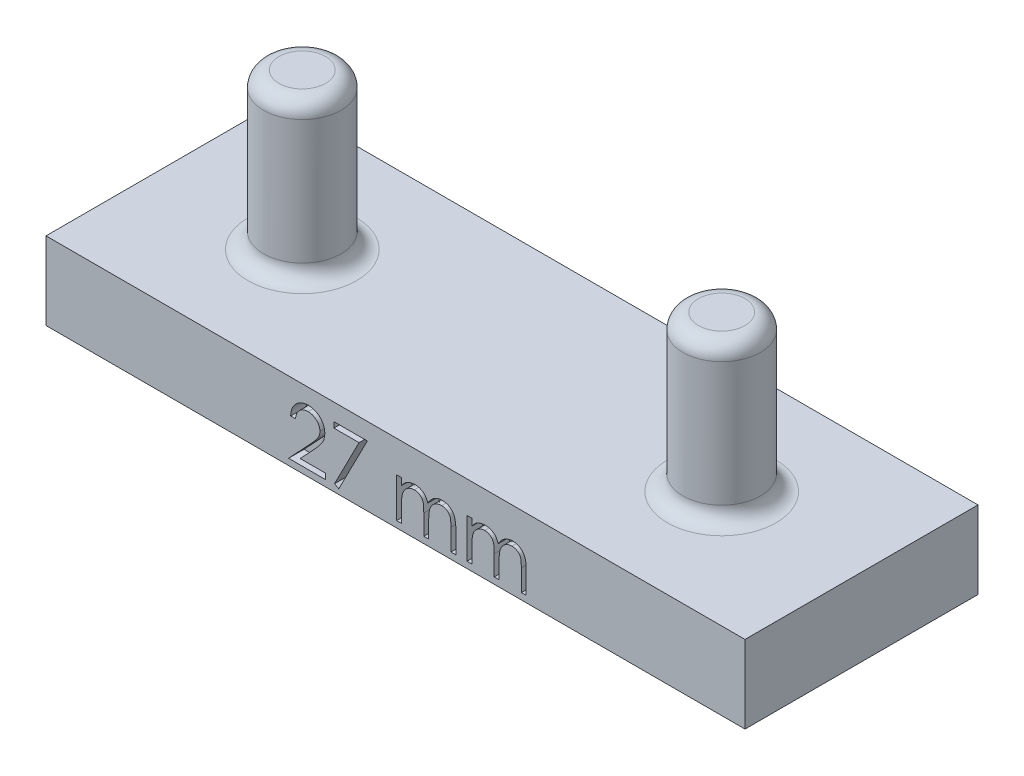
SolidWorks part; units mm, degrees
ref_plane "Front Plane" through (0, 0, 0) normal (0, 0, 1) x (1, 0, 0)
ref_plane "Top Plane" through (0, 0, 0) normal (0, 1, 0) x (1, 0, 0)
ref_plane "Right Plane" through (0, 0, 0) normal (1, 0, 0) x (0, 0, -1)
sketch "Sketch1" plane through (0, 0, 0) normal (0, 1, 0) x (1, 0, 0)
  circle A0 centre (-41.8213, 3.1021) radius 2.5
  circle A1 centre (-14.8213, 3.1021) radius 2.5
  dimension "D1" = 27
extrude "Boss-Extrude1" add sketch "Sketch1" along normal blind 10
sketch "Sketch2" plane through (0, 0, 0) normal (0, -1, 0) x (1, 0, 0)
  line L1 (-50.8213, 4.3979) -> (-5.8213, 4.3979)
  line L2 (-50.8213, 4.3979) -> (-50.8213, -10.6021)
  line L3 (-50.8213, -10.6021) -> (-5.8213, -10.6021)
  line L4 (-5.8213, 4.3979) -> (-5.8213, -10.6021)
  circle A0 centre (-41.8213, -3.1021) radius 2.5 construction
  dimension "D1" = 45
  dimension "D2" = 15
  dimension "D3" = 7.5
  dimension "D4" = 9
extrude "Boss-Extrude2" add sketch "Sketch2" along normal blind 5
sketch "Sketch3" plane through (0, 0, 4.3979) normal (0, 0, 1) x (1, 0, 0)
  line L0 (-7.1347, -4.5918) -> (-47.7505, -4.5918) construction
  text T0 "27 mm"
extrude "Cut-Extrude1" cut sketch "Sketch3" against normal blind 1
fillet "Fillet1" radius 1 4 edges at (-41.8213, 0, -0.6021) (-14.8213, 0, -5.6021) (-14.8213, 10, -0.6021) (-41.8213, 10, -0.6021)
